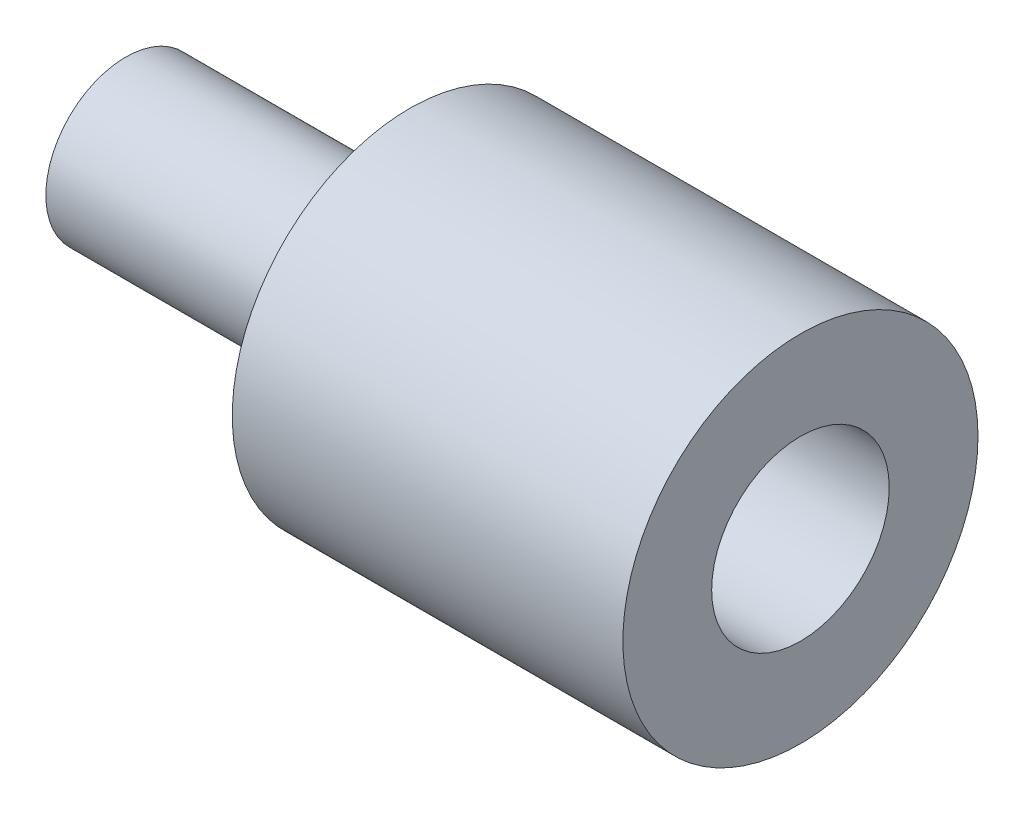
SolidWorks part; units mm, degrees
ref_plane "Front Plane" through (0, 0, 0) normal (0, 0, 1) x (1, 0, 0)
ref_plane "Top Plane" through (0, 0, 0) normal (0, 1, 0) x (1, 0, 0)
ref_plane "Right Plane" through (0, 0, 0) normal (1, 0, 0) x (0, 0, -1)
ref_axis "X" through (88.99, 0, 0) along (-1, 0, 0)
ref_axis "Y" through (0, 55, 0) along (0, -1, 0)
ref_axis "Z" through (0, 0, -88.99) along (0, 0, 1)
sketch "Sketch1" plane through (0, 0, 0) normal (0, 0, 1) x (1, 0, 0)
  line L0 (0, 0) -> (-65.6168, 0) construction
  line L1 (-65.6168, 0) -> (-68.1784, 17.7343) construction
  line L2 (0, 0) -> (0, 4.5)
  line L3 (0, 4.5) -> (16, 4.5)
  line L4 (16, 4.5) -> (16, 10)
  line L5 (16, 10) -> (38, 10)
  line L6 (38, 10) -> (38, 5)
  line L7 (38, 5) -> (22, 5)
  line L8 (22, 5) -> (22, 0)
  line L9 (22, 0) -> (0, 0)
  dimension "D1" = 9
  dimension "D2" = 10
  dimension "D3" = 16
  dimension "D4" = 6
  dimension "D5" = 16
  dimension "D6" = 20
revolve "Revolve1" add sketch "Sketch1" angle 360 about L0
